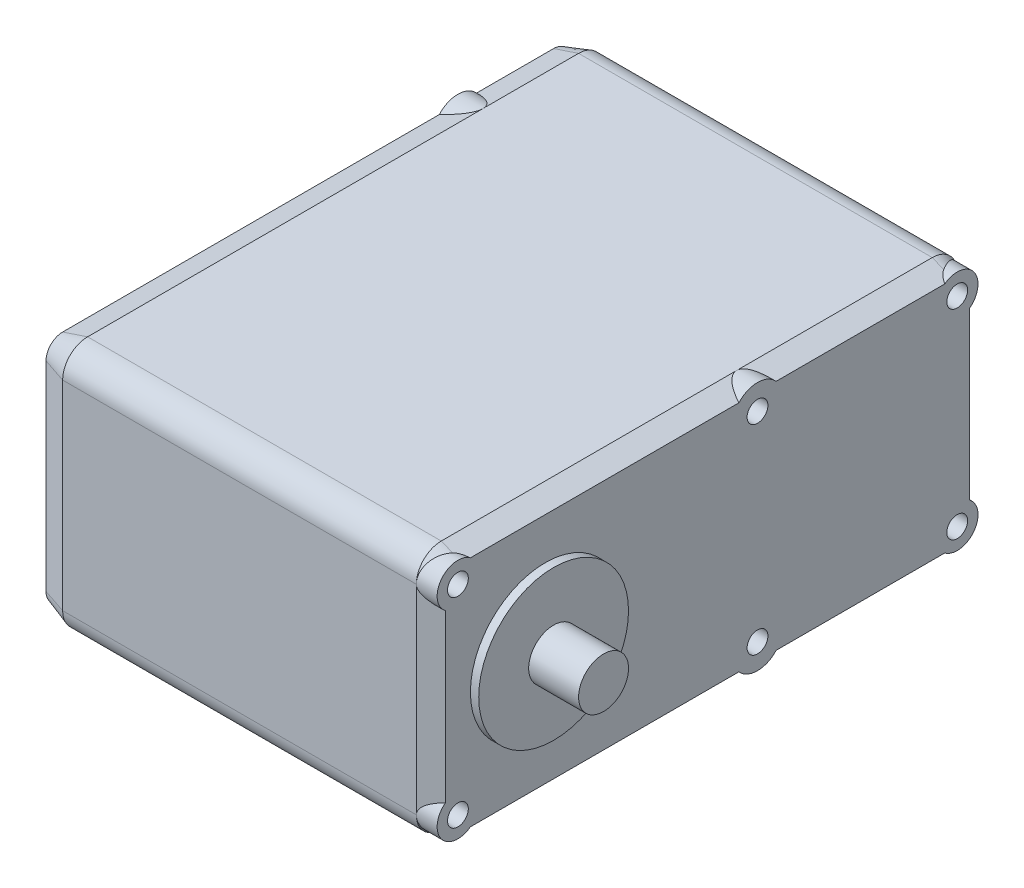
SolidWorks part; units mm, degrees
ref_plane "Front Plane" through (0, 0, 0) normal (0, 0, 1) x (1, 0, 0)
ref_plane "Top Plane" through (0, 0, 0) normal (0, 1, 0) x (1, 0, 0)
ref_plane "Right Plane" through (0, 0, 0) normal (1, 0, 0) x (0, 0, -1)
sketch "Sketch1" plane through (0, 0, 0) normal (0, 1, 0) x (1, 0, 0)
  line L1 (24, -32.5) -> (-24, -32.5)
  line L2 (24, -32.5) -> (24, 32.5)
  line L3 (24, 32.5) -> (-24, 32.5)
  line L4 (-24, -32.5) -> (-24, 32.5)
  line L5 (24, -32.5) -> (-24, 32.5) construction
  line L6 (24, 32.5) -> (-24, -32.5) construction
  point P0 (0, 0)
extrude "Boss-Extrude1" add sketch "Sketch1" along normal blind 30
fillet "Fillet2" radius 3 4 edges at (0, 30, -32.5) (0, 0, -32.5) (0, 0, 32.5) (0, 30, 32.5)
sketch "Sketch2" plane through (-24, 0, 0) normal (-1, 0, 0) x (0, 0, 1)
  line L0 (32.5, 15) -> (19.5, 15) construction
  line L1 (32.5, 27) -> (32.5, 3) construction
  circle A0 centre (19.5, 15) radius 9
extrude "Boss-Extrude2" add sketch "Sketch2" along normal blind 1
sketch "Sketch3" plane through (-25, 0, 0) normal (-1, 0, 0) x (0, 0, 1)
  line L0 (15.5, 15) -> (23.5, 15) construction
  line L1 (19.5, 19) -> (19.5, 11) construction
  circle A0 centre (19.5, 15) radius 4 construction
  point P6 (19.5, 15)
  point P9 (19.5, 15)
sketch "Sketch4" plane through (24, 0, 0) normal (1, 0, 0) x (0, 0, -1)
  circle A0 centre (-19.5, 15) radius 9 construction
  circle A1 centre (-19.5, 15) radius 9
extrude "Boss-Extrude4" add sketch "Sketch4" along normal blind 1
sketch "Sketch5" plane through (25, 0, 0) normal (1, 0, 0) x (0, 0, -1)
  circle A0 centre (-19.5, 15) radius 3
extrude "Boss-Extrude5" add sketch "Sketch5" along normal blind 6
chamfer "Chamfer1" distance 3 angle 18.435 8 edges at (-24, 0, 0) (-24, 29.1213, -31.6213) (-24, 15, -32.5) (-24, 0.8787, -31.6213) (-24, 30, 0) (-24, 29.1213, 31.6213) (-24, 15, 32.5) (-24, 0.8787, 31.6213) first distance on face at (0, 0, 0) first distance on face at (0, 28.8107, -31.3107) first distance on face at (0, 15, -32.5) first distance on face at (0, 1.1893, -31.3107) first distance on face at (0, 30, 0) first distance on face at (0, 28.8107, 31.3107) first distance on face at (0, 15, 32.5) first distance on face at (0, 1.1893, 31.3107)
chamfer "Chamfer2" distance 1 angle 45 1 edges at (-25, 15, 28.5)
chamfer "Chamfer3" distance 2.5 angle 21.8 8 edges at (24, 0.8787, -31.6213) (24, 15, -32.5) (24, 29.1213, -31.6213) (24, 30, 0) (24, 29.1213, 31.6213) (24, 15, 32.5) (24, 0.8787, 31.6213) (24, 0, 0) first distance on face at (1.5, 1.1893, -31.3107) first distance on face at (1.5, 15, -32.5) first distance on face at (1.5, 28.8107, -31.3107) first distance on face at (1.5, 30, 0) first distance on face at (1.5, 28.8107, 31.3107) first distance on face at (1.5, 15, 32.5) first distance on face at (1.5, 1.1893, 31.3107) first distance on face at (1.5, 0, 0)
sketch "Sketch6" plane through (24, 0, 0) normal (1, 0, 0) x (0, 0, -1)
  line L1 (-29.5, 30) -> (29.5, 30) construction
  line L2 (29.5, 0) -> (-29.5, 0) construction
  line L3 (0, 0) -> (0, 30) construction
  line L4 (30, 3) -> (30, 27) construction
  line L5 (-30, 27) -> (-30, 3) construction
  line L6 (31.5001, 15) -> (-31.5001, 15) construction
  line L7 (-31.5001, 27) -> (-31.5001, 3) construction
  line L8 (-32.5, 3) -> (-32.5, 27) construction
  line L9 (6, 27) -> (6, 3) construction
  line L10 (32.5, 27) -> (32.5, 3) construction
  circle A4 centre (6, 27) radius 3
  circle A5 centre (6, 3) radius 3
  circle A8 centre (-30, 3) radius 2.5
  arc A10 (-32.5, 3) -> (-29.5, 0) centre (-29.5, 3) ccw construction
  circle A11 centre (-30, 27) radius 2.5
  arc A12 (-29.5, 30) -> (-32.5, 27) centre (-29.5, 27) ccw construction
  circle A13 centre (30, 27) radius 2.5
  circle A14 centre (30, 3) radius 2.5
  point P3 (30, 15)
  point P10 (-30, 15)
  point P27 (0, 15)
  point P31 (6, 15)
  dimension "D1" = 2.5
  dimension "D2" = 2.5
  dimension "D3" = 24
extrude "Boss-Extrude6" add sketch "Sketch6" against normal blind 2.5
sketch "Sketch7" plane through (-24, 0, 0) normal (-1, 0, 0) x (0, 0, 1)
  line L0 (-32.5, 3) -> (-32.5, 27) construction
  line L2 (-31.5, 27) -> (-31.5, 3) construction
  line L3 (-30, 15) -> (-31.5, 15) construction
  line L4 (-30, 15) -> (-30, 3) construction
  line L5 (-30, 3) -> (-18, 3) construction
  line L6 (29.5, 0) -> (-29.5, 0) construction
  line L7 (-30, 15) -> (-30, 27) construction
  line L8 (-30, 27) -> (-18, 27) construction
  line L9 (-29.5, 30) -> (29.5, 30) construction
  circle A0 centre (-30, 15) radius 2.5
  circle A1 centre (-18, 3) radius 3
  circle A2 centre (-18, 27) radius 3
  dimension "D1" = 12
  dimension "D2" = 12
  dimension "D3" = 12
extrude "Boss-Extrude7" add sketch "Sketch7" against normal blind 3
sketch "Sketch8" plane through (-24, 0, 0) normal (-1, 0, 0) x (0, 0, 1)
  circle A0 centre (-18, 27) radius 1.25
  circle A1 centre (-30, 15) radius 1.25
  circle A2 centre (-18, 3) radius 1.25
  point P9 (0, 0)
extrude "Cut-Extrude1" cut sketch "Sketch8" against normal blind 5
sketch "Sketch10" plane through (24, 0, 0) normal (1, 0, 0) x (0, 0, -1)
  circle A0 centre (6, 3) radius 1.25
  circle A1 centre (30, 3) radius 1.25
  circle A2 centre (6, 27) radius 1.25
  circle A3 centre (30, 27) radius 1.25
  circle A4 centre (-30, 3) radius 1.25
  circle A5 centre (-30, 27) radius 1.25
  point P18 (0, 0)
  point P19 (0, 0)
  point P20 (0, 0)
  point P21 (0, 0)
  point P22 (0, 0)
  point P23 (0, 0)
  point P24 (0, 0)
  point P25 (0, 0)
  point P26 (0, 0)
extrude "Cut-Extrude2" cut sketch "Sketch10" against normal blind 5
